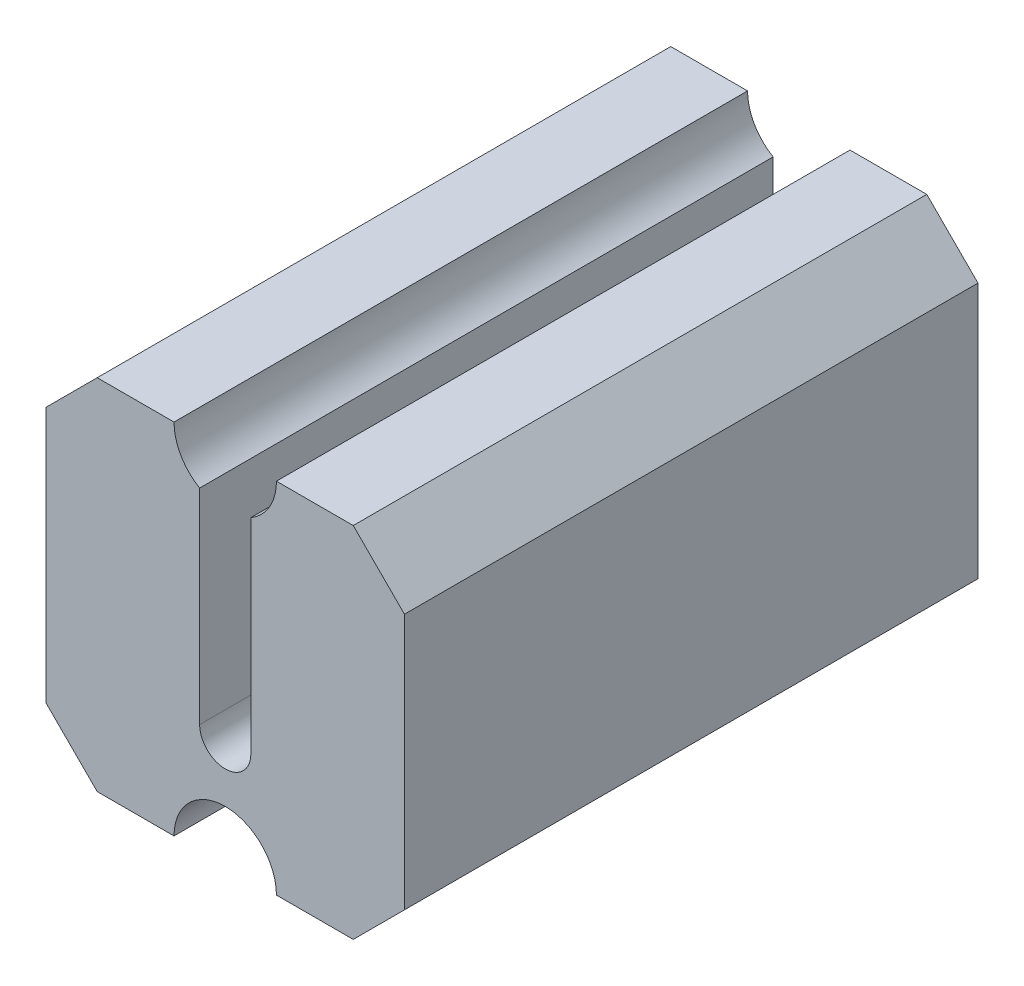
SolidWorks part; units mm, degrees
ref_plane "Front Plane" through (0, 0, 0) normal (0, 0, 1) x (1, 0, 0)
ref_plane "Top Plane" through (0, 0, 0) normal (0, 1, 0) x (1, 0, 0)
ref_plane "Right Plane" through (0, 0, 0) normal (1, 0, 0) x (0, 0, -1)
sketch "Sketch1" plane through (0, 0, 0) normal (0, 0, 1) x (1, 0, 0)
  line L0 (125, 175) -> (50, 175)
  line L1 (-125, -175) -> (-50, -175)
  line L2 (-175, -125) -> (-175, 125)
  line L3 (0, 0) -> (0, -70.9541) construction
  line L4 (175, -125) -> (175, 125)
  line L5 (-175, 0) -> (175, 0) construction
  line L6 (0, -93.3013) -> (0, -125) construction
  line L7 (-125, 175) -> (-125, -175) construction
  line L8 (-25, 131.6987) -> (-25, -68.3013)
  line L9 (-175, 125) -> (-25, 125) construction
  line L10 (125, 175) -> (125, -175) construction
  line L11 (-175, -125) -> (175, -125) construction
  line L12 (-125, 175) -> (-175, 125)
  line L13 (125, 175) -> (175, 125)
  line L14 (125, -175) -> (175, -125)
  line L15 (-125, -175) -> (-175, -125)
  line L16 (50, -175) -> (125, -175)
  line L17 (-50, 175) -> (-125, 175)
  line L18 (25, 131.6987) -> (25, -68.3013)
  line L19 (25, 125) -> (175, 125) construction
  arc A0 (-50, 175) -> (-25, 131.6987) centre (0, 175) ccw
  arc A1 (50, -175) -> (-50, -175) centre (0, -175) ccw
  arc A2 (-25, -68.3013) -> (25, -68.3013) centre (0, -68.3013) ccw
  arc A3 (25, 131.6987) -> (50, 175) centre (0, 175) ccw
  dimension "D1" = 350
  dimension "D5" = 50
  dimension "D6" = 25
  dimension "D8" = 50
  dimension "D2" = 350
  dimension "D3" = 50
  dimension "D4" = 50
  dimension "D7" = 200
  dimension "D9" = 0
  dimension "D10" = 75
  dimension "D11" = 75
  dimension "D12" = 100
  dimension "D13" = 50
  dimension "D14" = 0
extrude "Boss-Extrude1" add sketch "Sketch1" along normal blind 360 and the other way blind 200
ref_plane "Plane1" through (0, -175, 0) normal (0, -1, 0) x (-1, 0, 0)
